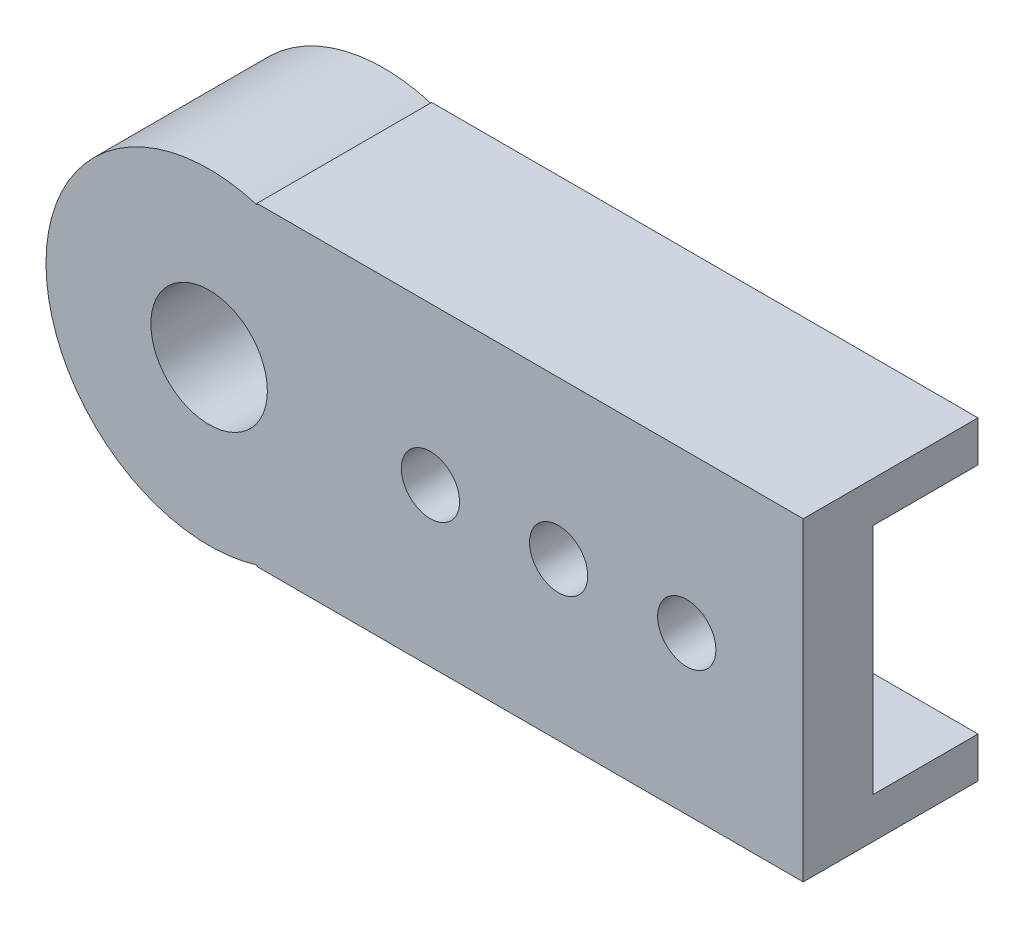
SolidWorks part; units mm, degrees
ref_plane "前视基准面" through (0, 0, 0) normal (0, 0, 1) x (1, 0, 0)
ref_plane "上视基准面" through (0, 0, 0) normal (0, 1, 0) x (1, 0, 0)
ref_plane "右视基准面" through (0, 0, 0) normal (1, 0, 0) x (0, 0, -1)
sketch "草图1" plane through (0, 0, 0) normal (0, 0, 1) x (1, 0, 0)
  line L1 (20, -10) -> (-20, -10)
  line L2 (20, -10) -> (20, 10)
  line L3 (20, 10) -> (-20, 10)
  line L4 (-20, -10) -> (-20, 10)
  line L5 (20, -10) -> (-20, 10) construction
  line L6 (20, 10) -> (-20, -10) construction
  point P0 (0, 0)
  dimension "D1" = 40
  dimension "D2" = 20
extrude "凸台-拉伸1" add sketch "草图1" along normal blind 6
sketch "草图2" plane through (0, 0, 6) normal (0, 0, 1) x (1, 0, 0)
  line L0 (20, -10) -> (20, 10) construction
  circle A0 centre (10, 0) radius 2.5
  circle A1 centre (-1, 0) radius 2.5
  circle A2 centre (-12, 0) radius 2.5
  dimension "D1" = 10
  dimension "D2" = 5
  dimension "D3" = 3
extrude "切除-拉伸1" cut sketch "草图2" against normal through all
sketch "草图3" plane through (0, 0, 6) normal (0, 0, 1) x (1, 0, 0)
  line L0 (20, 13.5) -> (20, 10)
  line L1 (20, -13.5) -> (-26.894, -13.5)
  line L3 (20, 13.5) -> (-26.894, 13.5)
  line L4 (-20, 10) -> (-20, -10)
  line L5 (-20, -10) -> (20, -10)
  line L6 (20, -10) -> (20, 10)
  line L7 (20, 10) -> (-20, 10)
  line L8 (-20, 10) -> (-20, -10)
  line L9 (-20, -10) -> (20, -10)
  line L10 (20, -10) -> (20, 10)
  line L11 (20, 10) -> (-20, 10)
  line L12 (-26.894, -13.5) -> (-26.894, 13.5)
  line L13 (20, -10.0394) -> (-26.894, 13.5) construction
  line L14 (20, 10.0394) -> (-26.894, -13.5) construction
  line L15 (20, -10) -> (20, -13.5)
  circle A0 centre (-31, 0) radius 11
  circle A1 centre (-31, 0) radius 14
  point P2 (0, 0)
  line M10 (-20, 10) -> (-20, -10)
  line M11 (-20, -10) -> (20, -10)
  line M13 (20, 10) -> (-20, 10)
  dimension "D3" = 22
  dimension "D4" = 28
  dimension "D2" = 3.5
  dimension "D1" = 0
extrude "凸台-拉伸2" add sketch "草图3" against normal blind 15 contours L3 A1 L1 L12 A0 | A1 L1 L15 M11 M10 | L1 A1 L8 A0 L12 | L8 A1 L3 L12 A0 | L8 A1 | A1 L0 L3 M10 M13 region at (-1.9449, 11.7771, 6) region at (-1.9449, -11.7771, 6) region at (-23.0173, 9.0328, 6) region at (-27.2274, 11.7946, 6) region at (-18.7882, 0, 6) region at (-23.0173, -9.0328, 6)
sketch "草图5" plane through (0, 0, 6) normal (0, 0, 1) x (1, 0, 0)
  circle A0 centre (-31, 0) radius 10
  circle A1 centre (-31, 0) radius 11 construction
  circle A2 centre (-31, 0) radius 11
  dimension "D1" = 20
sketch "草图6" plane through (0, 0, 6) normal (0, 0, 1) x (1, 0, 0)
  circle A0 centre (-31, 0) radius 5
  circle A1 centre (-31, 0) radius 11 construction
  circle A2 centre (-31, 0) radius 11
  dimension "D1" = 10
extrude "凸台-拉伸3" add sketch "草图6" against normal blind 8
